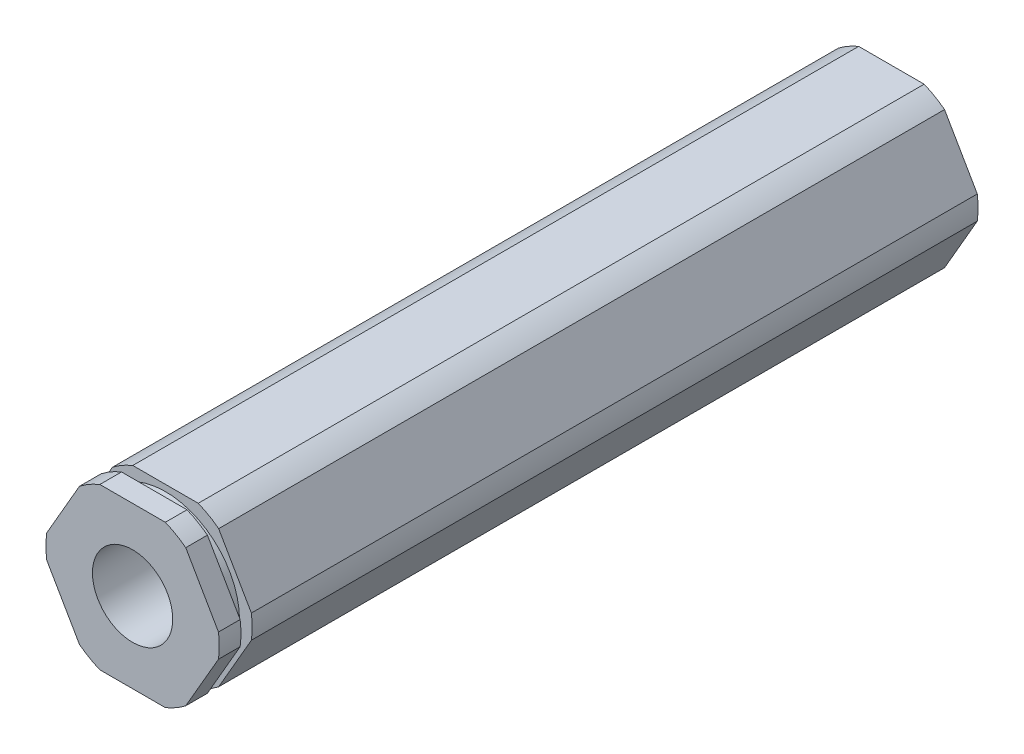
SolidWorks part; units mm, degrees
ref_plane "Front Plane" through (0, 0, 0) normal (0, 0, 1) x (1, 0, 0)
ref_plane "Top Plane" through (0, 0, 0) normal (0, 1, 0) x (1, 0, 0)
ref_plane "Right Plane" through (0, 0, 0) normal (1, 0, 0) x (0, 0, -1)
sketch "Sketch1" plane through (0, 0, 0) normal (0, 0, 1) x (1, 0, 0)
  line L1 (3.6662, 6.35) -> (-3.6662, 6.35)
  line L2 (-3.6662, 6.35) -> (-7.3323, 0)
  line L3 (-7.3323, 0) -> (-3.6662, -6.35)
  line L4 (-3.6662, -6.35) -> (3.6662, -6.35)
  line L5 (3.6662, -6.35) -> (7.3323, 0)
  line L6 (7.3323, 0) -> (3.6662, 6.35)
  circle A0 centre (0, 0) radius 6.35 construction
  circle A1 centre (0, 0) radius 3.175
  circle A2 centre (0, 0) radius 6.35 construction
  circle A3 centre (0, 0) radius 6.858
  dimension "D1" = 12.7
  dimension "D2" = 6.35
  dimension "D3" = 13.716
extrude "Boss-Extrude1" add sketch "Sketch1" along normal mid plane 60.0304 contours L6 A3 L1 L2 L3 L4 L5 A1 region at (3.3355, 5.7773, 0)
sketch "Sketch2" plane through (0, 0, 0) normal (1, 0, 0) x (0, 0, -1)
  line L0 (-2.4056, 0) -> (1.6345, 0) construction
  line L1 (-28.3007, 6.858) -> (-27.4117, 6.858)
  line L2 (-28.3007, 6.858) -> (-28.3007, 5.8547)
  line L3 (-28.3007, 5.8547) -> (-27.4117, 5.8547)
  line L4 (-27.4117, 6.858) -> (-27.4117, 5.8547)
  line L6 (-30.0152, 0.9317) -> (-30.0152, -0.9317) construction
  point P7 (-30.0152, 0)
  dimension "D1" = 0.889
  dimension "D2" = 5.8547
  dimension "D3" = 1.7145
  dimension "D4" = 1.0033
revolve "Cut-Revolve1" cut sketch "Sketch2" angle 360 about L0
